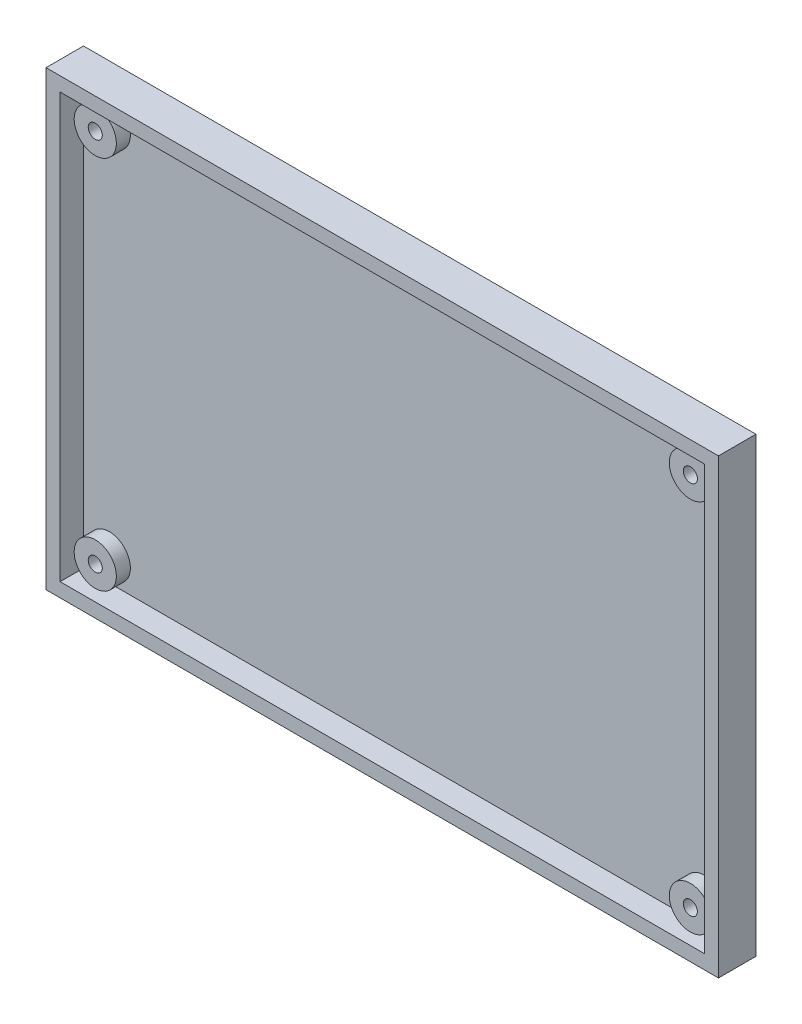
SolidWorks part; units mm, degrees
ref_plane "Front Plane" through (0, 0, 0) normal (0, 0, 1) x (1, 0, 0)
ref_plane "Top Plane" through (0, 0, 0) normal (0, 1, 0) x (1, 0, 0)
ref_plane "Right Plane" through (0, 0, 0) normal (1, 0, 0) x (0, 0, -1)
sketch "Sketch1" plane through (0, 0, 0) normal (0, 0, 1) x (1, 0, 0)
  line L1 (0, 0) -> (143.5, 0)
  line L2 (0, 0) -> (0, 96.5)
  line L3 (0, 96.5) -> (143.5, 96.5)
  line L4 (143.5, 0) -> (143.5, 96.5)
  circle A0 centre (8.5, 88) radius 1.5
  circle A1 centre (8.5, 8) radius 1.5
  circle A2 centre (135.5, 8) radius 1.5
  circle A3 centre (135.5, 88) radius 1.5
  dimension "D7" = 3
  dimension "D1" = 96.5
  dimension "D2" = 143.5
  dimension "D3" = 8.5
  dimension "D4" = 8.5
  dimension "D5" = 8
  dimension "D6" = 8
extrude "Boss-Extrude1" add sketch "Sketch1" along normal blind 8
shell "Shell1" thickness 3 removed face at (71.75, 48.25, 8)
sketch "Sketch2" plane through (0, 0, 8) normal (0, 0, 1) x (1, 0, 0)
  line L1 (3, 3) -> (140.5, 3)
  line L2 (3, 3) -> (3, 93.5)
  line L3 (3, 93.5) -> (140.5, 93.5)
  line L4 (140.5, 3) -> (140.5, 93.5)
extrude "Cut-Extrude1" cut sketch "Sketch2" against normal blind 2
